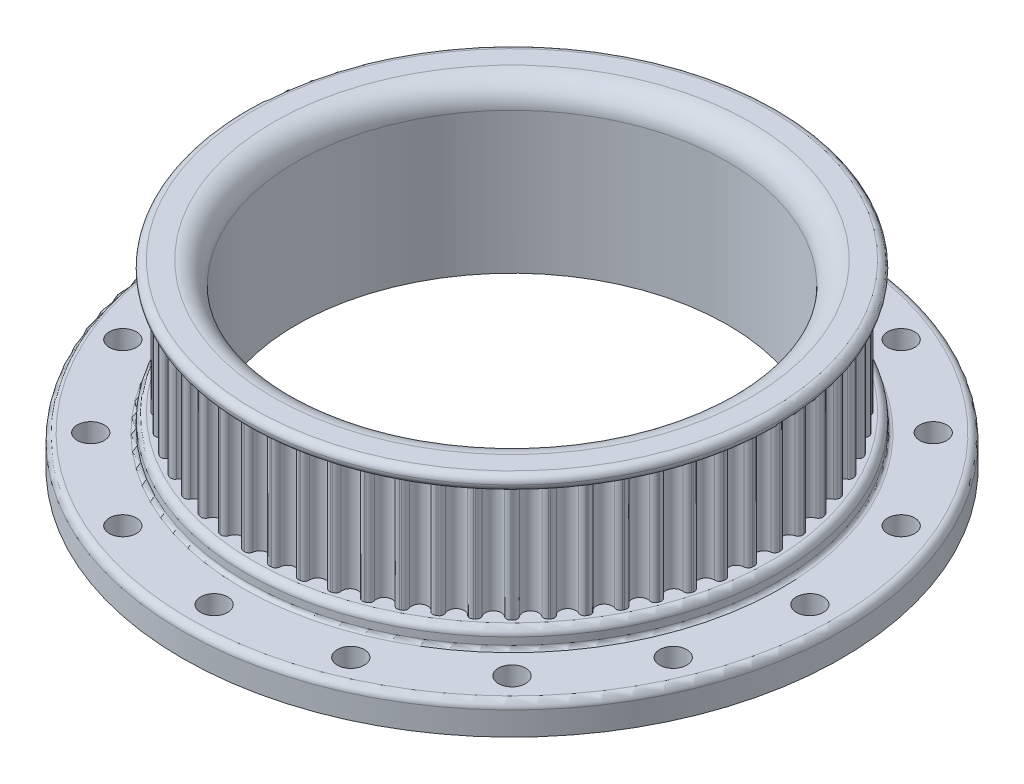
SolidWorks part; units mm, degrees
ref_plane "Front Plane" through (0, 0, 0) normal (0, 0, 1) x (1, 0, 0)
ref_plane "Top Plane" through (0, 0, 0) normal (0, 1, 0) x (1, 0, 0)
ref_plane "Right Plane" through (0, 0, 0) normal (1, 0, 0) x (0, 0, -1)
sketch "Sketch1" plane through (0, 0, 0) normal (0, 1, 0) x (1, 0, 0)
  line L0 (0, 0) -> (0, 28.2667) construction
  line L1 (0, 0) -> (2.9202, 27.7837) construction
  circle A0 centre (0, 0) radius 28.2667 construction
  circle A1 centre (0, 0) radius 27.0467 construction
  circle A2 centre (0, 27.9367) radius 0.89 construction
  circle A5 centre (2.9202, 27.7837) radius 0.89 construction
  arc A6 (0, 27.0467) -> (0.8804, 27.8061) centre (0, 27.9367) ccw
  arc A7 (0.8804, 27.8061) -> (1.3997, 28.2321) centre (1.3749, 27.7327) cw
  arc A8 (1.559, 28.2237) -> (2.031, 27.7458) centre (1.5314, 27.7245) cw
  arc A9 (2.8272, 26.8986) -> (2.031, 27.7458) centre (2.9202, 27.7837) cw
  arc A10 (1.3997, 28.2321) -> (1.559, 28.2237) centre (0, 0) cw
  arc A11 (0, 27.0467) -> (2.8272, 26.8986) centre (0, 0) ccw
  dimension "D1" = 56.5335
  dimension "D3" = 1.78
  dimension "D4" = 0.5
  dimension "D2" = 1.22
  dimension "D5" = 6
extrude "Boss-Extrude1" add sketch "Sketch1" along normal mid plane 13 contours A6 A11 A9 A8 A7 region at (0.001, 0, -0.0192)
ref_axis "Axis1" through (0, 3.3, 0) along (0, -1, 0)
pattern_circular "CirPattern1" count 60 over 360 about axis through (0, 3.3, 0) along (0, -1, 0) of "Boss-Extrude1"
sketch "Sketch2" plane through (0, 0, 0) normal (1, 0, 0) x (0, 0, -1)
  line L10 (0, 6.5) -> (29.4415, 6.5) construction
  line L11 (0, 6.5) -> (0, 8.0875) construction
  line L12 (0, 8.0875) -> (29.4415, 8.0875) construction
  line L15 (29.4415, 6.5) -> (29.4415, 8.0875) construction
  line L20 (0, 3.3) -> (0, -3.3) construction
  line L22 (29.4415, 8.0875) -> (0, 8.0875)
  line L23 (29.4415, 8.0875) -> (29.4415, 6.5)
  line L24 (29.4415, 6.5) -> (0, 6.5)
  line L25 (0, 8.0875) -> (0, 6.5)
  dimension "D1" = 1.5875
  dimension "D2" = 29.4415
  dimension "D3" = 6.5
revolve "Revolve3" add sketch "Sketch2" angle 360 about axis through (0, 3.3, 0) along (0, -1, 0) region at (0, 7.2937, -14.7207)
mirror "Mirror1" about plane through (0, 0, 0) normal (0, 1, 0) of "Revolve3"
sketch "Sketch3" plane through (0, 0, 0) normal (0, -1, 0) x (-1, 0, 0)
  circle A0 centre (0, 0) radius 23.8852
  dimension "D1" = 47.7705
extrude "Cut-Extrude1" cut sketch "Sketch3" against normal through all both and the other way through all
sketch "Sketch5" plane through (0, 0, 0) normal (0, 0, 1) x (1, 0, 0)
  line L0 (29.4415, -6.5) -> (-29.4415, -6.5) construction
  line L1 (-29.854, -8.5) -> (-36.5125, -8.5)
  line L2 (-36.5125, -8.5) -> (-36.5125, -10.0875)
  line L3 (-36.5125, -10.0875) -> (-23.8852, -10.0875)
  line L4 (-23.8852, -10.0875) -> (-23.8852, -8.0875)
  line L5 (-29.4415, -8.0875) -> (29.4415, -8.0875) construction
  line L6 (-23.8852, -8.0875) -> (-29.4415, -8.0875)
  arc A0 (-29.4415, -8.0875) -> (-29.854, -8.5) centre (-29.854, -8.0875) cw
  dimension "D1" = 2
  dimension "D2" = 36.5125
  dimension "D3" = 1.5875
revolve "Revolve4" add sketch "Sketch5" angle 360 about axis through (0, 3.3, 0) along (0, -1, 0)
sketch "Sketch6" plane through (0, -8.5, 0) normal (0, 1, 0) x (1, 0, 0)
  line L0 (-30.488, 12.6286) -> (0, 0) construction
  line L1 (0, 0) -> (-36.5125, 0) construction
  circle A0 centre (-30.488, 12.6286) radius 1.5
  circle A1 centre (0, 0) radius 36.5125 construction
  dimension "D2" = 3
  dimension "D1" = 33
  dimension "D3" = 22.5
extrude "Cut-Extrude2" cut sketch "Sketch6" against normal through all
pattern_circular "CirPattern2" count 16 over 360 about axis through (0, 3.3, 0) along (0, -1, 0) of "Cut-Extrude2"
fillet "Fillet1" radius 2.54 1 edges at (0, 8.0875, -23.8852)
sketch "Sketch9" plane through (0, -10.0875, 0) normal (0, -1, 0) x (1, 0, 0)
  circle A1 centre (0, 0) radius 36.5125
  circle A2 centre (0, 0) radius 29
  circle A3 centre (-30.488, -12.6286) radius 1.5
  circle A4 centre (-30.488, -12.6286) radius 1.5
  circle A5 centre (-23.3345, -23.3345) radius 1.5
  circle A6 centre (-23.3345, -23.3345) radius 1.5
  circle A7 centre (23.3345, 23.3345) radius 1.5
  circle A8 centre (23.3345, 23.3345) radius 1.5
  circle A9 centre (12.6286, 30.488) radius 1.5
  circle A10 centre (12.6286, 30.488) radius 1.5
  circle A11 centre (0, 33) radius 1.5
  circle A12 centre (0, 33) radius 1.5
  circle A13 centre (-12.6286, 30.488) radius 1.5
  circle A14 centre (-12.6286, 30.488) radius 1.5
  circle A15 centre (-23.3345, 23.3345) radius 1.5
  circle A16 centre (-23.3345, 23.3345) radius 1.5
  circle A17 centre (-30.488, 12.6286) radius 1.5
  circle A18 centre (-30.488, 12.6286) radius 1.5
  circle A19 centre (-33, 0) radius 1.5
  circle A20 centre (-33, 0) radius 1.5
  circle A21 centre (30.488, 12.6286) radius 1.5
  circle A22 centre (30.488, 12.6286) radius 1.5
  circle A23 centre (33, 0) radius 1.5
  circle A24 centre (33, 0) radius 1.5
  circle A25 centre (30.488, -12.6286) radius 1.5
  circle A26 centre (30.488, -12.6286) radius 1.5
  circle A27 centre (23.3345, -23.3345) radius 1.5
  circle A28 centre (23.3345, -23.3345) radius 1.5
  circle A29 centre (12.6286, -30.488) radius 1.5
  circle A30 centre (12.6286, -30.488) radius 1.5
  circle A31 centre (0, -33) radius 1.5
  circle A32 centre (0, -33) radius 1.5
  circle A33 centre (-12.6286, -30.488) radius 1.5
  circle A34 centre (-12.6286, -30.488) radius 1.5
  circle A35 centre (0, 0) radius 36.5125
  dimension "D18" = 58
  dimension "D2" = 0
  dimension "D3" = 0
  dimension "D4" = 0
  dimension "D5" = 0
  dimension "D6" = 0
  dimension "D7" = 0
  dimension "D8" = 0
  dimension "D9" = 0
  dimension "D10" = 0
  dimension "D11" = 0
  dimension "D12" = 0
  dimension "D13" = 0
  dimension "D14" = 0
  dimension "D15" = 0
  dimension "D16" = 0
  dimension "D17" = 0
  dimension "D19" = 0
extrude "Boss-Extrude2" add sketch "Sketch9" along normal up to surface (1.8125 mm away)
fillet "Fillet2" radius 0.7937 4 edges at (0, -6.5, 29.4415) (0, 6.5, 29.4415) (0, 8.0875, 29.4415) (0, -8.5, 36.5125)
equation "\"TEETH_NUM\"= 60"
equation "\"TOOTH_PITCH\"= 3mm"
equation "\"PITCH_LINE_OFFSET\"= .015in"
equation "\"DIAMETER_PER_GROOVE\"= \"OUTSIDE_DIAMETER\" / \"TEETH_NUM\" * 1in"
equation "\"PITCH_DIAMETER\"= ( ( \"TEETH_NUM\" * 3 - 1.31 ) / 3.1415 + .415 ) * 1mm"
equation "\"OUTSIDE_DIAMETER\"= \"PITCH_DIAMETER\" - \"PITCH_LINE_OFFSET\" * 2"
equation "\"D1@Sketch1\"=\"OUTSIDE_DIAMETER\""
equation "\"TOOTH_HEIGHT\"= 1.22mm"
equation "\"D2@Sketch1\"=\"TOOTH_HEIGHT\""
equation "\"TOOTH_DIAMETER\"= 1.78mm"
equation "\"INTERNAL_RADIUS\"= .5mm"
equation "\"D3@Sketch1\"=\"TOOTH_DIAMETER\""
equation "\"D5@Sketch1\"=360 / \"TEETH_NUM\""
equation "\"D4@Sketch1\"=\"INTERNAL_RADIUS\""
equation "\"D1@CirPattern1\"=\"TEETH_NUM\""
equation "\"BELT_GAP\"= 13mm"
equation "\"D2@Sketch2\"=\"PITCH_DIAMETER\"/2+1/32"
equation "\"D3@Sketch2\"=\"BELT_GAP\"/2"
equation "\"D1@Sketch3\"=\"PITCH_DIAMETER\"-.375"
equation "\"D1@Boss-Extrude1\"=\"BELT_GAP\""
equation "\"center_offset\"=0.75"
equation "\"Bearing_Diameter\"= 58mm"
equation "\"bolt_on_feature\"=16"
equation "\"D1@CirPattern2\"=\"bolt_on_feature\""
